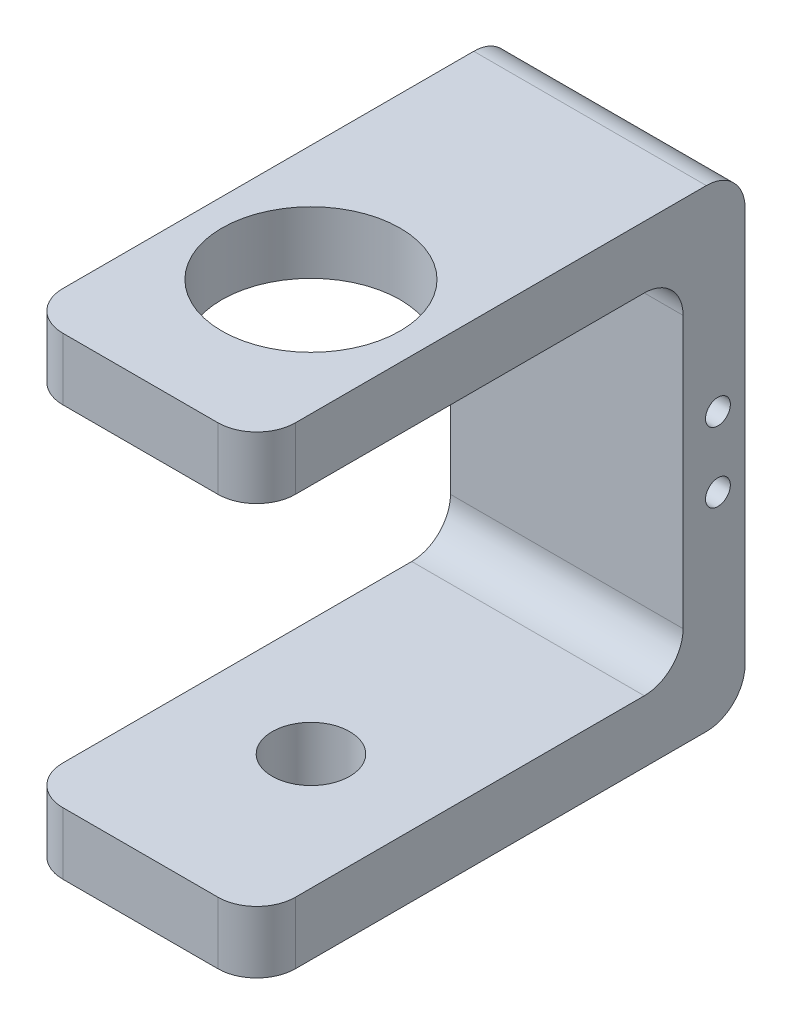
SolidWorks part; units mm, degrees
ref_plane "Front Plane" through (0, 0, 0) normal (0, 0, 1) x (1, 0, 0)
ref_plane "Top Plane" through (0, 0, 0) normal (0, 1, 0) x (1, 0, 0)
ref_plane "Right Plane" through (0, 0, 0) normal (1, 0, 0) x (0, 0, -1)
sketch "Sketch1" plane through (0, 0, 0) normal (1, 0, 0) x (0, 0, -1)
  line L0 (0, 0) -> (55, 0)
  line L1 (55, 0) -> (55, -45)
  line L2 (55, -45) -> (0, -45)
  line L3 (0, -45) -> (0, -53)
  line L4 (0, -53) -> (63, -53)
  line L5 (63, -53) -> (63, 8)
  line L6 (63, 8) -> (0, 8)
  line L7 (0, 8) -> (0, 0)
  dimension "D1" = 55
  dimension "D2" = 45
  dimension "D3" = 8
  dimension "D4" = 8
extrude "Boss-Extrude1" add sketch "Sketch1" along normal blind 30 contours L0 L1 L2 L3 L4 L5 L6 L7
sketch "Sketch2" plane through (0, 8, 0) normal (0, 1, 0) x (1, 0, 0)
  line L0 (30, 0) -> (0, 0) construction
  line L1 (30, 63) -> (0, 63) construction
  circle A0 centre (15, 22) radius 11.5
  point P2 (15, 0)
  dimension "D1" = 23
  dimension "D2" = 41
extrude "Cut-Extrude1" cut sketch "Sketch2" against normal up to next
sketch "Sketch3" plane through (0, -45, 0) normal (0, 1, 0) x (1, 0, 0)
  circle A0 centre (15, 22) radius 5
  circle A1 centre (15, 22) radius 11.5 construction
  dimension "D1" = 10
extrude "Cut-Extrude2" cut sketch "Sketch3" against normal up to next contours A0
sketch "Sketch4" plane through (30, 0, 0) normal (1, 0, 0) x (0, 0, -1)
  line L0 (63, -53) -> (63, 8) construction
  circle A2 centre (59.5, -27) radius 1.6
  circle A3 centre (59.5, -18) radius 1.6
  point P6 (63, -22.5)
  dimension "D1" = 9
  dimension "D4" = 3.2
  dimension "D2" = 3.5
  dimension "D3" = 4.5
extrude "Cut-Extrude3" cut sketch "Sketch4" against normal up to next contours A2 | A3 region at (30, -27, -59.5)
fillet "Fillet1" radius 5 6 edges at (15, -53, -63) (15, 8, -63) (0, -49, 0) (0, 4, 0) (30, -49, 0) (30, 4, 0)
fillet "Fillet2" radius 5 2 edges at (15, 0, -55) (15, -45, -55)
